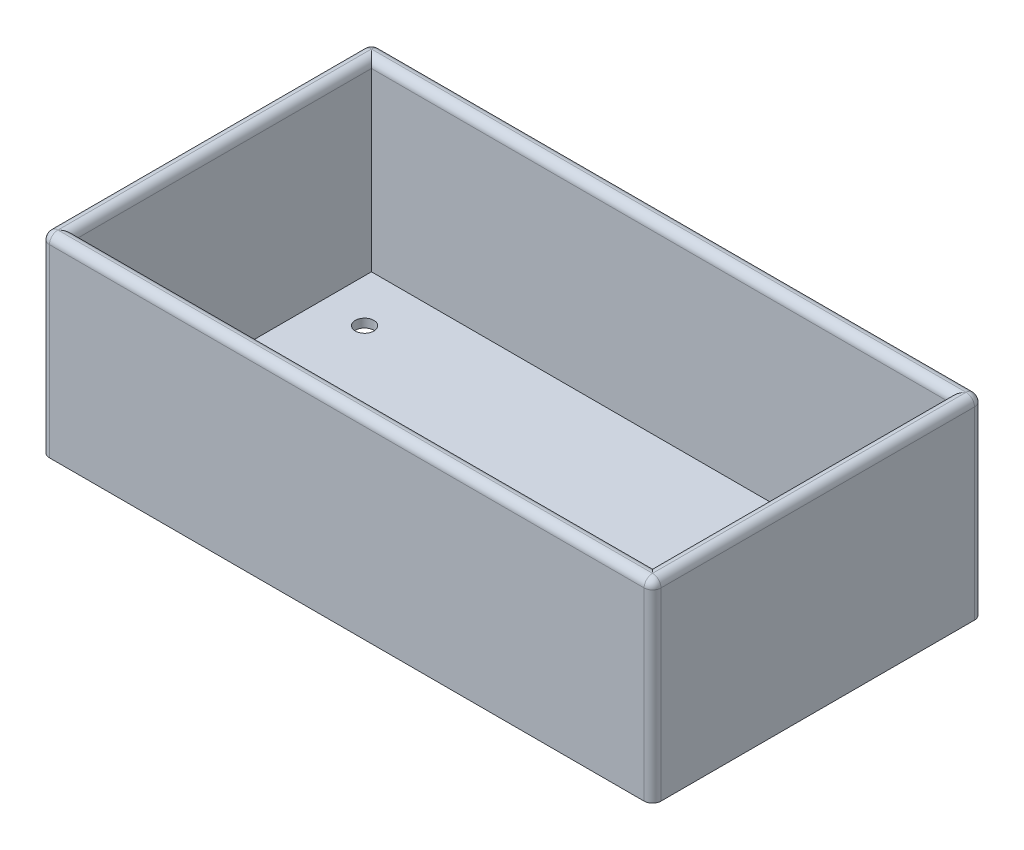
SolidWorks part; units mm, degrees
ref_plane "Front Plane" through (0, 0, 0) normal (0, 0, 1) x (1, 0, 0)
ref_plane "Top Plane" through (0, 0, 0) normal (0, 1, 0) x (1, 0, 0)
ref_plane "Right Plane" through (0, 0, 0) normal (1, 0, 0) x (0, 0, -1)
sketch "Sketch1" plane through (0, 0, 0) normal (0, 1, 0) x (1, 0, 0)
  line L1 (0, 0) -> (72.39, 0)
  line L2 (0, 0) -> (0, 39.116)
  line L3 (0, 39.116) -> (72.39, 39.116)
  line L4 (72.39, 0) -> (72.39, 39.116)
  dimension "D1" = 72.39
  dimension "D2" = 39.116
extrude "Boss-Extrude1" add sketch "Sketch1" along normal blind 22.86
sketch "Sketch2" plane through (0, 22.86, 0) normal (0, 1, 0) x (1, 0, 0)
  line L0 (0, 0) -> (72.39, 0) construction
  line L1 (2, 2) -> (70.39, 2)
  line L2 (2, 2) -> (2, 37.116)
  line L3 (2, 37.116) -> (70.39, 37.116)
  line L4 (70.39, 2) -> (70.39, 37.116)
  line L5 (0, 39.116) -> (0, 0) construction
  line L6 (72.39, 0) -> (72.39, 39.116) construction
  line L7 (72.39, 39.116) -> (0, 39.116) construction
  point P4 (36.195, 2)
  dimension "D1" = 2
  dimension "D2" = 2
  dimension "D3" = 2
  dimension "D4" = 2
extrude "Cut-Extrude1" cut sketch "Sketch2" against normal blind 21.844 contours L2 L1 L4 L3
fillet "Fillet1" radius 1 12 edges at (36.195, 22.86, -39.116) (72.39, 22.86, -19.558) (36.195, 22.86, 0) (0, 22.86, -19.558) (70.39, 22.86, -19.558) (36.195, 22.86, -37.116) (2, 22.86, -19.558) (36.195, 22.86, -2) (72.39, 11.43, 0) (72.39, 11.43, -39.116) (0, 11.43, 0) (0, 11.43, -39.116)
hole_wizard "Tap Drill for M2.5x0.45 Tap1" positions "Sketch5" profile "Sketch6" hole size "M2.5x0.45" standard "ANSI Metric" end condition through all
sketch "Sketch5" plane through (0, 1.016, 0) normal (0, 1, 0) x (1, 0, 0)
  point P0 (7.1189, 31.1852)
  point P2 (7.1189, 7.1852)
  point P4 (65.1189, 31.1852)
  point P6 (65.1189, 7.1852)
  point P7 (0, 0)
  point P8 (0, 0)
  point P9 (0, 0)
  point P10 (0, 0)
  dimension "D1" = 24
  dimension "D2" = 24
  dimension "D3" = 58
  dimension "D4" = 58
sketch "Sketch6" plane through (7.1189, 1.016, -31.1852) normal (1, 0, 0) x (0, 0, 1)
  line L0 (0, 0) -> (0, 1.016)
  line L1 (0, 1.016) -> (1.1, 1.016)
  line L2 (1.1, 1.016) -> (1.1, 0)
  line L5 (1.1, 0) -> (0, 0)
  line L11 (0, -6.35) -> (0, 107.95) construction
  dimension "Thru Hole Dia." = 2.2
  dimension "Thru Hole Depth" = 1.016
